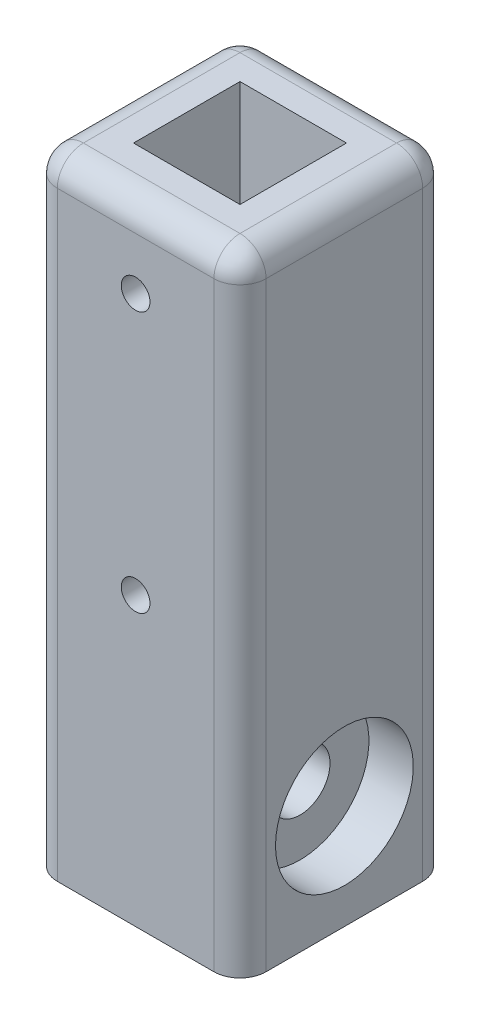
SolidWorks part; units mm, degrees
ref_plane "Front Plane" through (0, 0, 0) normal (0, 0, 1) x (1, 0, 0)
ref_plane "Top Plane" through (0, 0, 0) normal (0, 1, 0) x (1, 0, 0)
ref_plane "Right Plane" through (0, 0, 0) normal (1, 0, 0) x (0, 0, -1)
sketch "Sketch1" plane through (0, 0, 0) normal (0, 1, 0) x (1, 0, 0)
  line L1 (0, 0) -> (20.4, 0)
  line L2 (0, 0) -> (0, 20.4)
  line L3 (0, 20.4) -> (20.4, 20.4)
  line L4 (20.4, 0) -> (20.4, 20.4)
  line L5 (-9.8, -9.8) -> (30.2, -9.8)
  line L6 (-9.8, -9.8) -> (-9.8, 30.2)
  line L7 (-9.8, 30.2) -> (30.2, 30.2)
  line L8 (30.2, -9.8) -> (30.2, 30.2)
  dimension "D1" = 40
  dimension "D2" = 40
  dimension "D3" = 20.4
  dimension "D4" = 20.4
  dimension "D5" = 9.8
  dimension "D6" = 9.8
extrude "Boss-Extrude1" add sketch "Sketch1" along normal blind 80
extrude "Boss-Extrude2" add sketch "Sketch1<2>" against normal blind 40 contours L1 L4 L3 L2 | L5 L8 L7 L6 L4 L1 L2 L3 region at (10.2, 0, -10.2) region at (-9.2343, 0, -10.2)
sketch "Sketch1<2>" plane through (0, 0, 0) normal (0, 1, 0) x (1, 0, 0) same geometry as "Sketch1"
sketch "Sketch2" plane through (0, 0, 0) normal (0, 0, -1) x (-1, 0, 0)
  line L0 (-30.2, 80) -> (9.8, 80) construction
  line L1 (-30.2, 15) -> (9.8, 15) construction
  line L2 (-30.2, 80) -> (-30.2, -40) construction
  line L3 (9.8, 80) -> (9.8, -40) construction
  circle A0 centre (-10.2, 15) radius 2.75
  circle A1 centre (-10.2, 65) radius 2.75
  point P14 (-10.2, 15)
  dimension "D1" = 5.5
  dimension "D2" = 5.5
  dimension "D3" = 15
  dimension "D4" = 15
extrude "Cut-Extrude1" cut sketch "Sketch2" against normal through all both and the other way through all
sketch "Sketch3" plane through (-9.8, 0, 0) normal (-1, 0, 0) x (0, 0, 1)
  line L0 (9.8, 80) -> (9.8, -40) construction
  line L1 (-30.2, -40) -> (9.8, -40)
  line L2 (-30.2, -40) -> (-30.2, 0)
  line L3 (-30.2, 0) -> (9.8, 0)
  line L4 (9.8, -40) -> (9.8, 0)
  circle A0 centre (-10.2, -20) radius 13.2
  circle A1 centre (-10.2, -20) radius 5.75
  point P11 (-10.2, -40)
  point P12 (-30.2, -20)
  dimension "D2" = 26.4
  dimension "D3" = 11.5
  dimension "D1" = 40
extrude "Cut-Extrude2" cut sketch "Sketch3" against normal blind 8.5 contours A0 A1 region at (-9.8, -20, -23.0266)
extrude "Cut-Extrude3" cut sketch "Sketch3<3>" along normal blind 8.5 from surface contours A0 A1 region at (-9.8, -20, -23.0266) starting at face at (30.2, 20, -10.2)
sketch "Sketch3<3>" plane through (-9.8, 0, 0) normal (-1, 0, 0) x (0, 0, 1) same geometry as "Sketch3"
extrude "Cut-Extrude4" cut sketch "Sketch3<4>" against normal through all contours A1 region at (-9.8, -20, -10.2)
sketch "Sketch3<4>" plane through (-9.8, 0, 0) normal (-1, 0, 0) x (0, 0, 1) same geometry as "Sketch3"
fillet "Fillet1" radius 5 4 edges at (-9.8, 20, -30.2) (-9.8, 20, 9.8) (30.2, 20, 9.8) (30.2, 20, -30.2)
fillet "Fillet2" radius 5 8 edges at (28.7355, 80, 8.3355) (10.2, 80, 9.8) (-8.3355, 80, 8.3355) (-9.8, 80, -10.2) (-8.3355, 80, -28.7355) (10.2, 80, -30.2) (28.7355, 80, -28.7355) (30.2, 80, -10.2)
